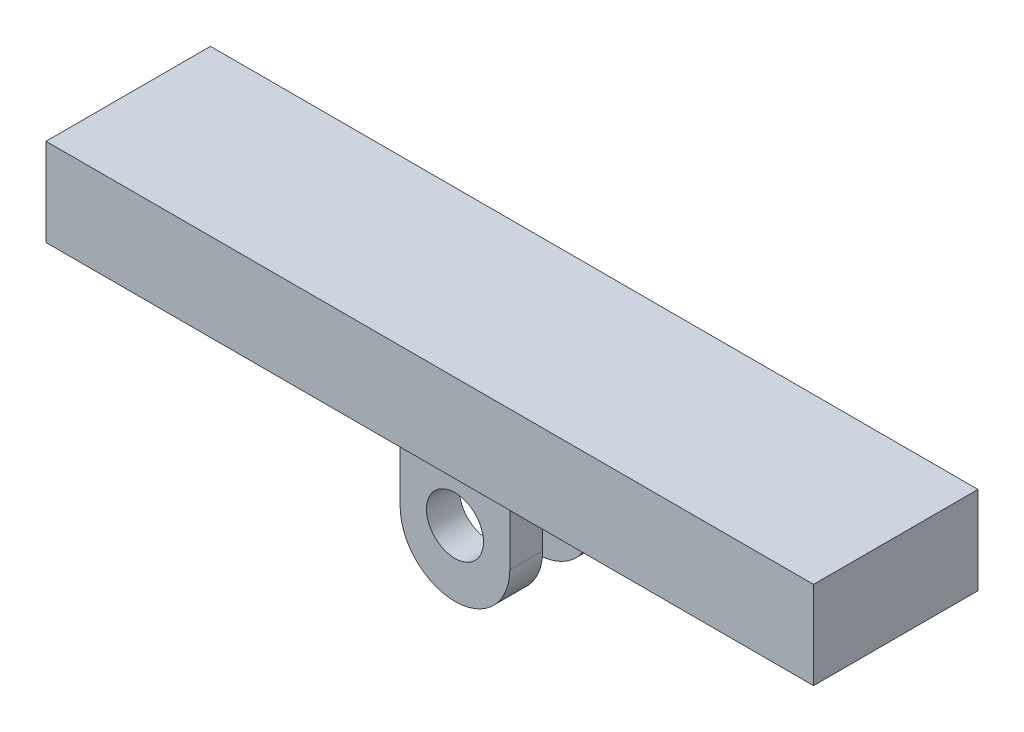
SolidWorks part; units mm, degrees
ref_plane "Front Plane" through (0, 0, 0) normal (1, 0, 0) x (0, 1, 0)
ref_plane "Top Plane" through (0, 0, 0) normal (0, 0, 1) x (0, 1, 0)
ref_plane "Right Plane" through (0, 0, 0) normal (0, 1, 0) x (-1, 0, 0)
sketch "Sketch1" plane through (0, 0, 0) normal (0, 0, 1) x (0, 1, 0)
  line L1 (-4, 35) -> (4, 35)
  line L2 (-4, 35) -> (-4, -35)
  line L3 (-4, -35) -> (4, -35)
  line L4 (4, 35) -> (4, -35)
  line L5 (-4, 35) -> (4, -35) construction
  line L6 (-4, -35) -> (4, 35) construction
  point P0 (0, 0)
  dimension "D1" = 8
  dimension "D2" = 70
extrude "Boss-Extrude1" add sketch "Sketch1" against normal blind 15
sketch "Sketch2" plane through (0, -4, 0) normal (0, -1, 0) x (1, 0, 0)
  line L0 (0, 0) -> (0, -15) construction
  line L1 (-35, -15) -> (35, -15) construction
  line L2 (-35, -7.5) -> (35, -7.5) construction
  line L3 (-35, -15) -> (-35, 0) construction
  line L4 (35, -15) -> (35, 0) construction
  line L5 (35, 0) -> (-35, 0) construction
  line L6 (-5, -2.3) -> (5, -2.3)
  line L7 (-5, -2.3) -> (-5, -5.3)
  line L8 (-5, -5.3) -> (5, -5.3)
  line L9 (5, -2.3) -> (5, -5.3)
  line L10 (-5, -2.3) -> (5, -5.3) construction
  line L11 (-5, -5.3) -> (5, -2.3) construction
  line L12 (-5, -9.8) -> (5, -9.8)
  line L13 (-5, -9.8) -> (-5, -12.8)
  line L14 (-5, -12.8) -> (5, -12.8)
  line L15 (5, -9.8) -> (5, -12.8)
  line L16 (-5, -9.8) -> (5, -12.8) construction
  line L17 (-5, -12.8) -> (5, -9.8) construction
  point P11 (0, -3.8)
  point P16 (0, -11.3)
  dimension "D1" = 10
  dimension "D2" = 10
  dimension "D3" = 4.5
  dimension "D4" = 2.3
  dimension "D5" = 11.2
  dimension "D6" = 3
extrude "Boss-Extrude2" add sketch "Sketch2" along normal blind 12
sketch "Sketch3" plane through (0, 0, -2.3) normal (0, 0, 1) x (1, 0, 0)
  line L0 (0, -16) -> (0, 0) construction
  line L1 (5, -16) -> (-5, -16) construction
  line L2 (5, -16) -> (5, -4) construction
  line L3 (5, -10) -> (-5, -10) construction
  line L4 (-5, -16) -> (-5, -4) construction
  circle A0 centre (0, -10) radius 2.6
  dimension "D1" = 5.2
extrude "Cut-Extrude1" cut sketch "Sketch3" against normal blind 12
fillet "Fillet1" radius 5 4 edges at (-5, -16, -11.3) (5, -16, -11.3) (5, -16, -3.8) (-5, -16, -3.8)
scale "Scale1" scale about centroid uniform scaling yes scale factor 0.7
